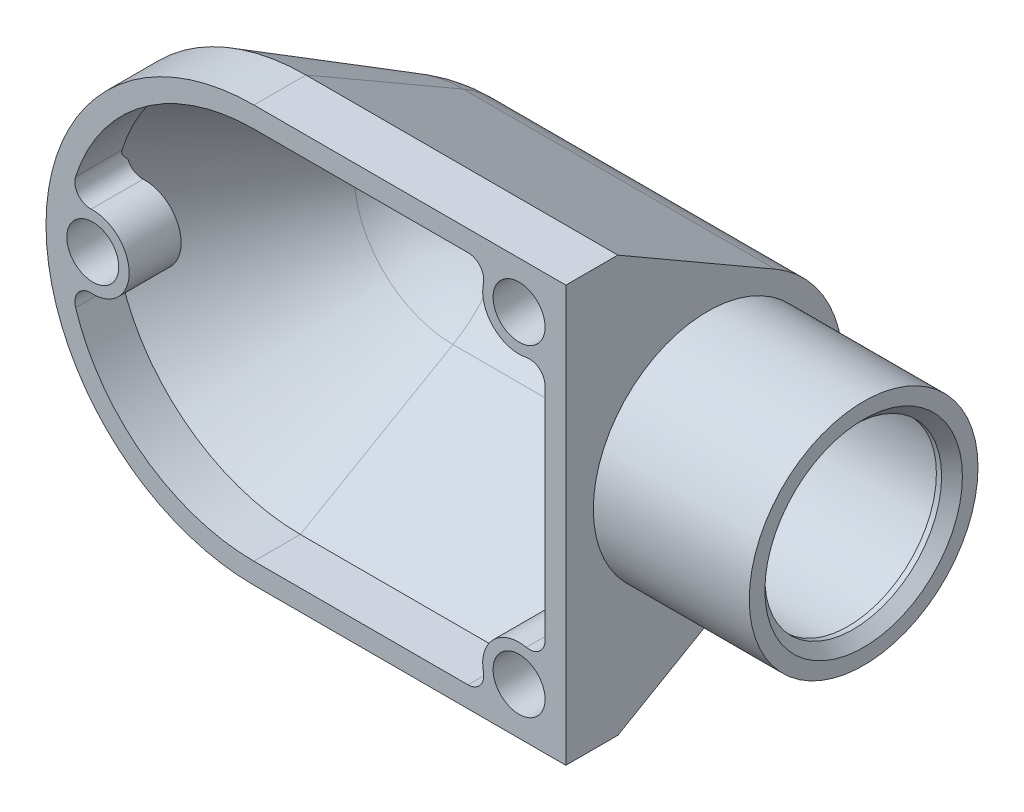
SolidWorks part; units mm, degrees
material "ABS"
ref_plane "前视基准面" through (0, 0, 0) normal (0, 0, 1) x (1, 0, 0)
ref_plane "上视基准面" through (0, 0, 0) normal (0, 1, 0) x (1, 0, 0)
ref_plane "右视基准面" through (0, 0, 0) normal (1, 0, 0) x (0, 0, -1)
other "Configuration Table"
sketch "草图4" plane through (0, 0, 0) normal (0, 0, 1) x (1, 0, 0)
  line L1 (15, 20) -> (-15, 20)
  line L2 (15, 20) -> (15, -20)
  line L3 (15, -20) -> (-15, -20)
  line L4 (-15, 20) -> (-15, -20) construction
  line L5 (15, 20) -> (-15, -20) construction
  line L6 (15, -20) -> (-15, 20) construction
  arc A0 (-15, 20) -> (-15, -20) centre (-15, 0) ccw
  point P0 (0, 0)
  dimension "D1" = 40
  dimension "D2" = 30
extrude "凸台-拉伸3" add sketch "草图4" along normal blind 5
sketch "草图5" plane through (15, 0, 0) normal (1, 0, 0) x (0, 0, -1)
  line L0 (0, 0) -> (8.641, 0) construction
  line L1 (0, 20) -> (15.141, 11.2583)
  line L2 (0, 20) -> (0, -20)
  line L3 (0, -20) -> (15.141, -11.2583)
  circle A0 centre (8.641, 0) radius 10 construction
  arc A1 (15.141, -11.2583) -> (15.141, 11.2583) centre (8.641, 0) ccw
  dimension "D1" = 20
  dimension "D2" = 3
  dimension "D3" = 60
extrude "凸台-拉伸4" add sketch "草图5" against normal blind 30
sketch "草图6" plane through (-15, 0, 0) normal (-1, 0, 0) x (0, 0, 1)
  line L0 (0, 0) -> (-21.7305, 0)
  line L3 (0, -20) -> (0, 20)
  line L4 (0, 20) -> (-15.141, 11.2583)
  line L5 (-15.141, -11.2583) -> (0, -20)
  line L6 (0, -20) -> (0, 20)
  line L7 (0, 20) -> (-15.141, 11.2583)
  line L8 (-15.141, -11.2583) -> (0, -20)
  arc A1 (-15.141, 11.2583) -> (-15.141, -11.2583) centre (-8.641, 0) ccw
  arc A2 (-15.141, 11.2583) -> (-15.141, -11.2583) centre (-8.641, 0) ccw
  dimension "D1" = 0
revolve "旋转2" add sketch "草图6" angle 180 about L0 region at (-15, 7.3692, -8.8328) reverse direction yes
sketch "草图7" plane through (15, 0, 0) normal (1, 0, 0) x (0, 0, -1)
  circle A0 centre (8.641, 0) radius 11
  arc A1 (15.141, -11.2583) -> (15.141, 11.2583) centre (8.641, 0) ccw construction
  dimension "D1" = 22
extrude "切除-拉伸1" cut sketch "草图7" against normal blind 10
shell "抽壳1" thickness 2 removed face at (5, 0, -19.641) removed face at (5, 0, -19.641) removed face at (-5, 0, 5)
sketch "草图8" plane through (0, 0, 5) normal (0, 0, 1) x (1, 0, 0)
  line L0 (-35, 0) -> (15, 0) construction
  line L1 (15, -20) -> (15, 20) construction
  line L2 (13, -18) -> (13, -9.5263) construction
  line L3 (-15, -18) -> (13, -18) construction
  circle A0 centre (10.5, 15.5) radius 2.5
  arc A1 (-15, 20) -> (-15, -20) centre (-15, 0) ccw construction
  circle A2 centre (-30.5, 0) radius 2.5
  circle A3 centre (10.5, -15.5) radius 2.5
  arc A4 (-15, 18) -> (-15, -18) centre (-15, 0) ccw construction
  circle A5 centre (-30.5, 0) radius 3.5
  circle A6 centre (10.5, 15.5) radius 3.5
  circle A7 centre (10.5, -15.5) radius 3.5
  dimension "D1" = 5
  dimension "D2" = 7
extrude "凸台-拉伸5" add sketch "草图8" against normal blind 5
fillet "圆角2" radius 1.5 6 edges at (13, -13.0505, 2.5) (8.0505, -18, 2.7679) (8.0505, 18, 2.7679) (13, 13.0505, 2.5) (-32.8065, -2.6325, 2.7679) (-32.8065, 2.6325, 2.7679)
sketch "草图9" plane through (15, 0, 0) normal (1, 0, 0) x (0, 0, -1)
  circle A0 centre (8.641, 0) radius 11
  circle A1 centre (8.641, 0) radius 9.5
  circle A3 centre (8.641, 0) radius 11 construction
  dimension "D1" = 1.5
extrude "凸台-拉伸6" add sketch "草图9" along normal blind 15 separate body
sketch "草图10" plane through (30, 0, 0) normal (1, 0, 0) x (0, 0, -1)
  circle A0 centre (8.641, 0) radius 8.5
  circle A2 centre (8.641, 0) radius 9.5
  circle A3 centre (8.641, 0) radius 9.5 construction
  dimension "D1" = 1
extrude "凸台-拉伸7" add sketch "草图10" against normal blind 1.5
chamfer "倒角1" distance 1 angle 45 1 edges at (30, 0, -17.141)
